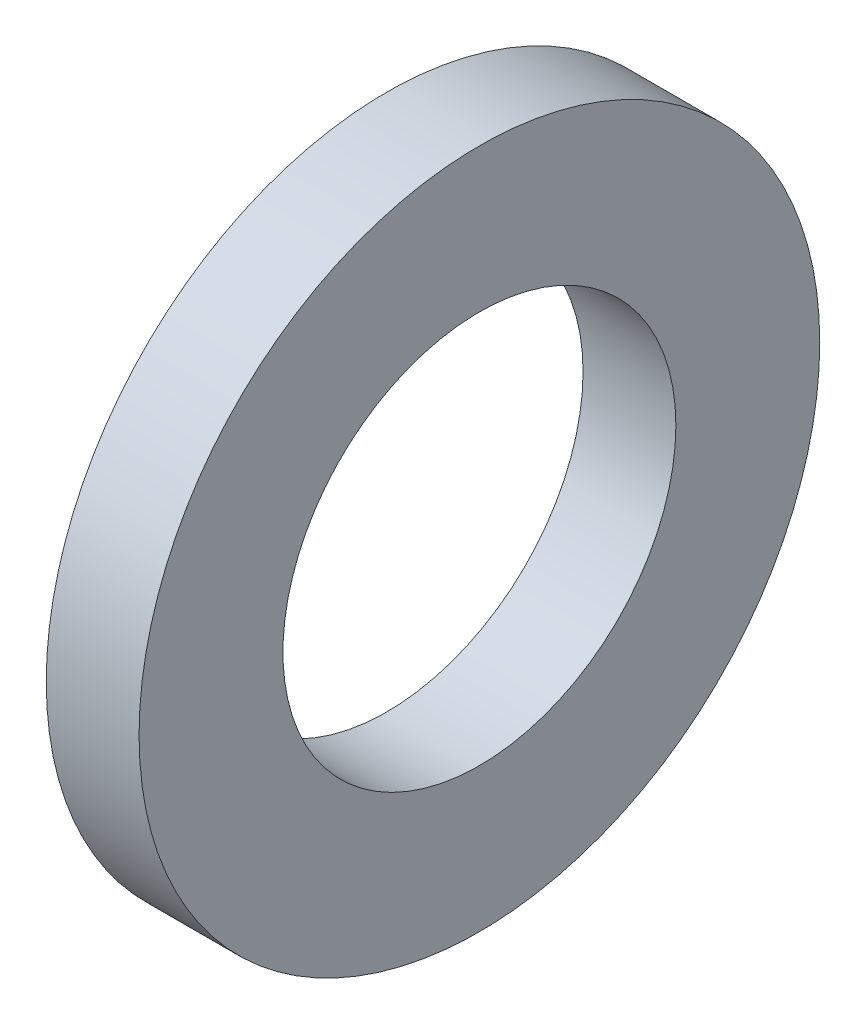
SolidWorks part; units mm, degrees
material "Nylon 101"
ref_plane "Front Plane" through (0, 0, 0) normal (0, 0, 1) x (1, 0, 0)
ref_plane "Top Plane" through (0, 0, 0) normal (0, 1, 0) x (1, 0, 0)
ref_plane "Right Plane" through (0, 0, 0) normal (1, 0, 0) x (0, 0, -1)
sketch "Sketch1" plane through (0, 0, 0) normal (1, 0, 0) x (0, 0, -1)
  circle A0 centre (0, 0) radius 11
  circle A1 centre (0, 0) radius 6.35
  dimension "D1" = 12.7
  dimension "D2" = 22
extrude "Boss-Extrude1" add sketch "Sketch1" along normal blind 1.5 and the other way blind 1.5
